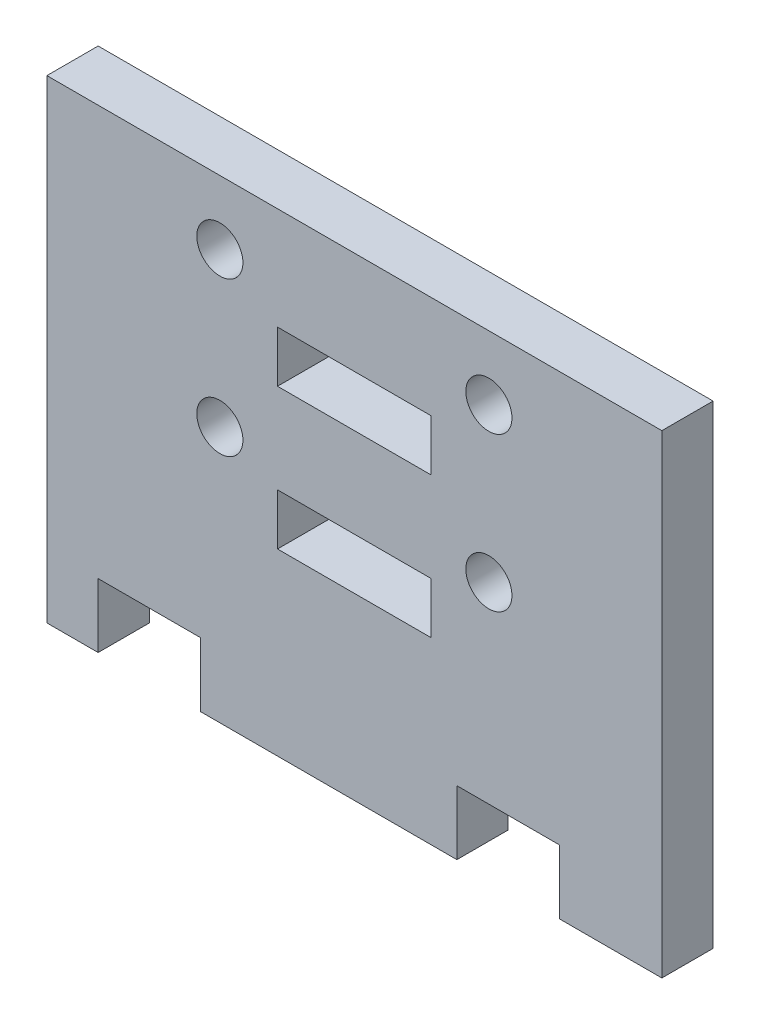
SolidWorks part; units mm, degrees
ref_plane "Front Plane" through (0, 0, 0) normal (0, 0, 1) x (1, 0, 0)
ref_plane "Top Plane" through (0, 0, 0) normal (0, 1, 0) x (1, 0, 0)
ref_plane "Right Plane" through (0, 0, 0) normal (1, 0, 0) x (0, 0, -1)
sketch "Sketch1" plane through (0, 0, 0) normal (0, 0, 1) x (1, 0, 0)
  line L22 (55.2401, 12.5) -> (55.2401, 9) construction
  line L23 (59.2401, 0) -> (49.2401, 0)
  line L24 (59.2401, 0) -> (59.2401, 2.5)
  line L25 (49.2401, 2.5) -> (45.2401, 2.5)
  line L26 (58.2401, 9) -> (58.2401, 7)
  line L27 (52.2401, 9) -> (58.2401, 9)
  line L28 (45.2401, 2.5) -> (45.2401, 0)
  line L29 (58.2401, 7) -> (52.2401, 7)
  line L30 (52.2401, 7) -> (52.2401, 9)
  line L31 (49.2401, 0) -> (49.2401, 2.5)
  line L32 (43.2401, 0) -> (43.2401, 18.5)
  line L33 (45.2401, 0) -> (43.2401, 0)
  line L34 (63.2401, 2.5) -> (63.2401, 0)
  line L35 (52.2401, 12.5) -> (52.2401, 14.5)
  line L36 (58.2401, 12.5) -> (52.2401, 12.5)
  line L37 (52.2401, 14.5) -> (58.2401, 14.5)
  line L38 (58.2401, 14.5) -> (58.2401, 12.5)
  line L39 (67.2401, 0) -> (67.2401, 18.5)
  line L40 (67.2401, 18.5) -> (43.2401, 18.5)
  line L41 (63.2401, 0) -> (67.2401, 0)
  line L42 (63.2401, 2.5) -> (59.2401, 2.5)
  circle A4 centre (60.4901, 10) radius 0.9
  circle A5 centre (49.9901, 16) radius 0.9
  circle A6 centre (49.9901, 10) radius 0.9
  circle A7 centre (60.4901, 16) radius 0.9
  dimension "D1" = 1.8
  dimension "D3" = 2
  dimension "D4" = 4
  dimension "D5" = 16
  dimension "D6" = 2.5
  dimension "D7" = 4
  dimension "D8" = 2
  dimension "D9" = 6
  dimension "D10" = 2.5
  dimension "D11" = 2.5
  dimension "D12" = 4.5
  dimension "D2" = 18.5
  dimension "D13" = 10.5
  dimension "D14" = 24
extrude "Boss-Extrude1" add sketch "Sketch1" along normal blind 2
equation "\"D13@Sketch1\"= \"fingerWidth@parametersSketch@prostheticParameters.SLDPRT\" - 5.7'Hole distance"
equation "\"D1@Sketch1\"= 1.5 + \"tol1@parametersSketch@prostheticParameters.SLDPRT\""
